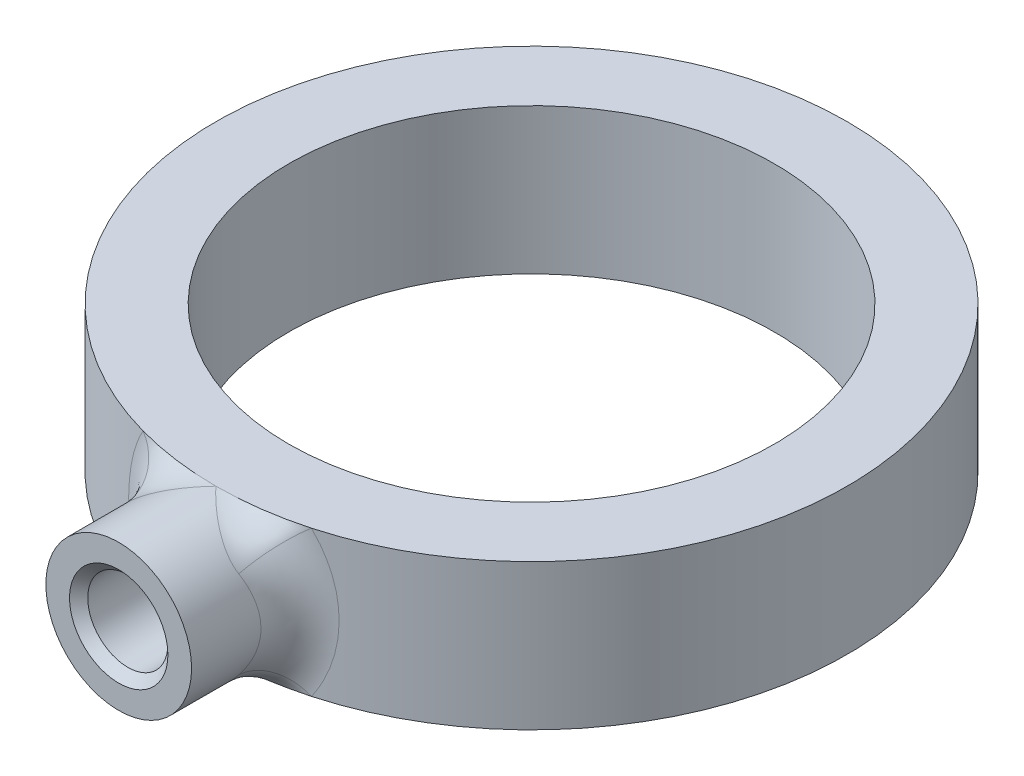
SolidWorks part; units mm, degrees
material "201 Annealed Stainless Steel (SS)"
ref_plane "Front Plane" through (0, 0, 0) normal (0, 0, 1) x (1, 0, 0)
ref_plane "Top Plane" through (0, 0, 0) normal (0, 1, 0) x (1, 0, 0)
ref_plane "Right Plane" through (0, 0, 0) normal (1, 0, 0) x (0, 0, -1)
sketch "Sketch1" plane through (0, 0, 0) normal (0, 1, 0) x (1, 0, 0)
  circle A0 centre (0, 0) radius 13
  circle A1 centre (0, 0) radius 10
  dimension "D1" = 26
  dimension "D2" = 20
extrude "Boss-Extrude1" add sketch "Sketch1" along normal mid plane 6
ref_plane "Plane1" through (0, 0, 17) normal (0, 0, 1) x (1, 0, 0)
sketch "Sketch3" plane through (0, 0, 17) normal (0, 0, 1) x (1, 0, 0)
  circle A0 centre (0, 0) radius 3
  dimension "D1" = 6
extrude "Boss-Extrude2" add sketch "Sketch3" against normal up to surface (4.3509 mm away) up to face at (0, 3, 13)
fillet "Fillet1" radius 2 2 edges at (-2.9743, 0.3916, 12.6552) (2.9196, 0.69, 12.6679)
hole_wizard "M4 Tapped Hole1" positions "Sketch6" profile "Sketch8" tap size "M4" standard "ISO"
sketch "Sketch6" plane through (0, 0, 17) normal (0, 0, 1) x (1, 0, 0)
  point P0 (0, 0)
sketch "Sketch8" plane through (0, 0, 17) normal (1, 0, 0) x (0, -1, 0)
  line L0 (0, 0) -> (0, 13.7914)
  line L1 (0, 13.7914) -> (1.65, 12.8)
  line L2 (1.65, 12.8) -> (1.65, 0.375)
  line L3 (1.65, 0.375) -> (2.025, 0)
  line L5 (2.025, 0) -> (0, 0)
  line L6 (-1.65, 0.375) -> (-2.025, 0) construction
  line L10 (0, 13.7914) -> (-1.65, 12.8) construction
  line L11 (0, -6.35) -> (0, 107.95) construction
  dimension "Tap Drill Dia." = 3.3
  dimension "Tap Drill Depth" = 12.8
  dimension "Near C'Sink Dia." = 4.05
  dimension "Near C'Sink Angle" = 90
  dimension "Drill Angle" = 118
cosmetic thread "Hole Thread1" parameters "D1"=8, "D2"=4
